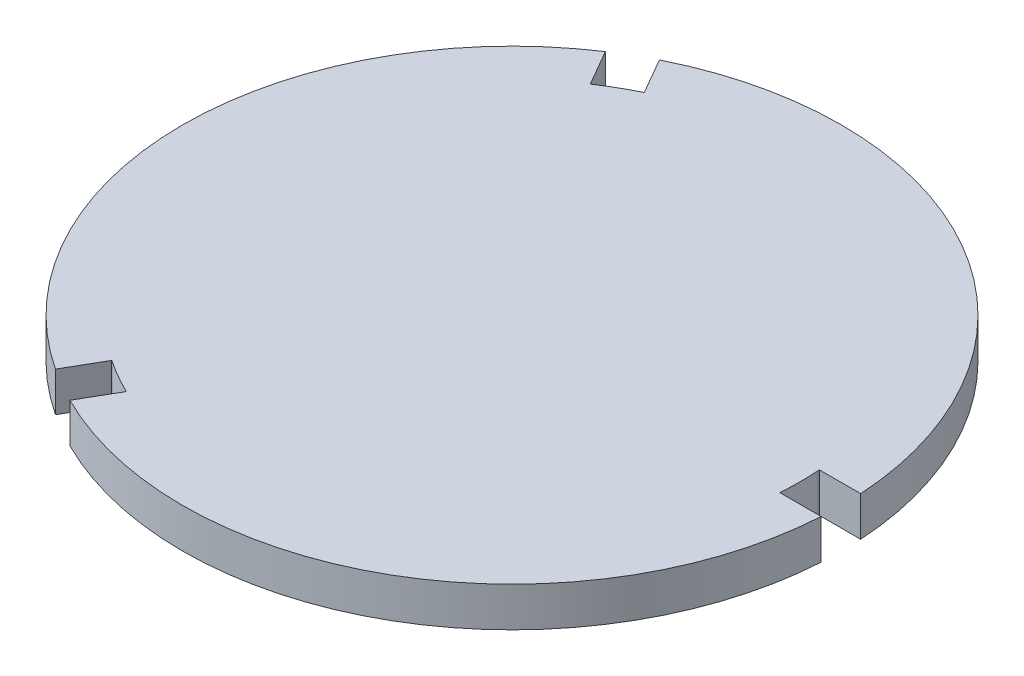
SolidWorks part; units mm, degrees
ref_plane "Front Plane" through (0, 0, 0) normal (0, 0, 1) x (1, 0, 0)
ref_plane "Top Plane" through (0, 0, 0) normal (0, 1, 0) x (1, 0, 0)
ref_plane "Right Plane" through (0, 0, 0) normal (1, 0, 0) x (0, 0, -1)
sketch "Sketch1" plane through (0, 0, 0) normal (0, 0, 1) x (1, 0, 0)
  line L0 (88.9, -138.3122) -> (88.9, -150.5042) construction
  line L1 (-88.9, -138.3122) -> (88.9, -138.3122) construction
  line L2 (-88.9, -150.5042) -> (88.9, -150.5042) construction
  line L3 (88.9, -138.3122) -> (88.9, -150.5042)
  line L4 (0, -138.3122) -> (88.9, -138.3122)
  line L5 (0, -150.5042) -> (88.9, -150.5042)
  line L7 (0, 0) -> (0, -150.5042) construction
  line L9 (0, -138.3122) -> (0, -150.5042)
revolve "Revolve1" add sketch "Sketch1" angle 360 about L7
sketch "Sketch2" plane through (0, -138.3122, 0) normal (0, 1, 0) x (1, 0, 0)
  line L0 (101.417, 6.096) -> (88.717, 6.096)
  line L2 (88.717, 6.096) -> (88.717, -6.096)
  line L3 (101.417, -6.096) -> (88.717, -6.096)
  line L4 (0, 0) -> (88.717, 0) construction
  line L5 (-55.9878, -84.7817) -> (-49.6378, -73.7831)
  line L6 (-39.0792, -79.8791) -> (-49.6378, -73.7831)
  line L7 (-45.4292, -90.8777) -> (-39.0792, -79.8791)
  line L8 (-45.4292, 90.8777) -> (-39.0792, 79.8791)
  line L9 (-49.6378, 73.7831) -> (-39.0792, 79.8791)
  line L10 (-55.9878, 84.7817) -> (-49.6378, 73.7831)
  arc A0 (101.417, 6.096) -> (-45.4292, 90.8777) centre (0, 0) ccw
  arc A2 (-55.9878, 84.7817) -> (-55.9878, -84.7817) centre (0, 0) ccw
  arc A3 (-45.4292, -90.8777) -> (101.417, -6.096) centre (0, 0) ccw
  point P18 (0, 0)
  dimension "D1" = 203.2
  dimension "D2" = 12.192
  dimension "D3" = 12.7
  dimension "D4" = 3
extrude "Boss-Extrude1" add sketch "Sketch2" against normal up to surface (12.192 mm away) contours A2 L5 L6 L7 A3 L3 L2 L0 A0 L8 L9 L10 up to face at (-88.9, -150.5042, 0)
